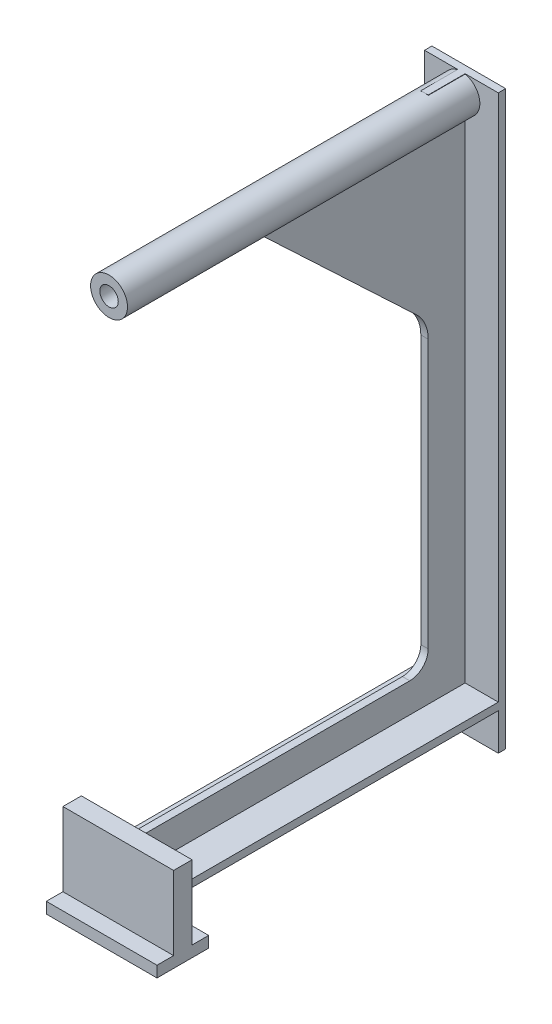
SolidWorks part; units mm, degrees
ref_plane "Front Plane" through (0, 0, 0) normal (0, 0, 1) x (1, 0, 0)
ref_plane "Top Plane" through (0, 0, 0) normal (0, 1, 0) x (1, 0, 0)
ref_plane "Right Plane" through (0, 0, 0) normal (1, 0, 0) x (0, 0, -1)
sketch "Sketch1" plane through (0, 0, 0) normal (1, 0, 0) x (0, 0, -1)
  line L0 (0, -17.2999) -> (0, 38.275) construction
  line L1 (-7, 1.5) -> (7, 1.5)
  line L2 (-7, 1.5) -> (-7, -1.5)
  line L3 (-7, -1.5) -> (7, -1.5)
  line L4 (7, 1.5) -> (7, -1.5)
  line L5 (-7, 1.5) -> (7, -1.5) construction
  line L6 (-7, -1.5) -> (7, 1.5) construction
  line L8 (-2.5, 21.5) -> (2.5, 21.5)
  line L9 (-2.5, 21.5) -> (-2.5, 1.5)
  line L10 (-2.5, 1.5) -> (2.5, 1.5)
  line L11 (2.5, 21.5) -> (2.5, 1.5)
  line L12 (-2.5, 21.5) -> (2.5, 1.5) construction
  line L13 (-2.5, 1.5) -> (2.5, 21.5) construction
  point P0 (0, 0)
  point P1 (0, 0)
  point P9 (0, 11.5)
  dimension "D1" = 5
  dimension "D2" = 20
  dimension "D3" = 14
  dimension "D4" = 3
extrude "Boss-Extrude1" add sketch "Sketch1" along normal blind 30 contours L11 L8 L9 L1 | L4 L1 L2 L3 region at (0, 0, 0) region at (0, 11.5, 0)
sketch "Sketch2" plane through (0, 0, 0) normal (0, 0, 1) x (1, 0, 0)
  line L0 (15, 1.5) -> (15, 32.2821) construction
  line L1 (30, 1.5) -> (0, 1.5) construction
  line L2 (0, 0) -> (39.1823, 0) construction
  circle A0 centre (15, 150) radius 5
  circle A1 centre (15, 150) radius 2.5
  point P4 (15, 150)
  dimension "D1" = 150
  dimension "D2" = 5
  dimension "D3" = 10
sketch "Sketch4" plane through (0, 0, 0) normal (0, 1, 0) x (1, 0, 0)
  line L0 (15, 0) -> (15, 14.6802) construction
  line L1 (30, 2.5) -> (0, 2.5) construction
  line L2 (14, 92.5) -> (16, 92.5)
  line L3 (14, 92.5) -> (14, 2.5)
  line L4 (14, 2.5) -> (16, 2.5)
  line L5 (16, 92.5) -> (16, 2.5)
  line L6 (14, 92.5) -> (16, 2.5) construction
  line L7 (14, 2.5) -> (16, 92.5) construction
  line L8 (15, 14.6802) -> (15, 36.8844) construction
  line L9 (14, 80.5) -> (16, 80.5)
  line L10 (5, 90.5) -> (25, 90.5)
  line L11 (5, 90.5) -> (5, 92.5)
  line L12 (5, 92.5) -> (25, 92.5)
  line L13 (25, 90.5) -> (25, 92.5)
  line L14 (5, 90.5) -> (25, 92.5) construction
  line L15 (5, 92.5) -> (25, 90.5) construction
  point P3 (15, 47.5)
  point P10 (15, 91.5)
  point P12 (15, 91.5)
  point P17 (15, 2.5)
  dimension "D1" = 2
  dimension "D2" = 90
  dimension "D3" = 89
  dimension "D4" = 2
  dimension "D5" = 20
  dimension "D6" = 78
extrude "Boss-Extrude2" add sketch "Sketch4" along normal blind 155 separate body contours L10 L13 L12 L5 | L3 L10 L5 L2 | L12 L11 L10 L3 | L10 L3 L9 L5 region at (15, 0, -91.5) region at (9.5, 0, -91.5) region at (20.5, 0, -91.5) region at (15, 0, -85.5)
extrude "Boss-Extrude3" add sketch "Sketch4<4>" along normal blind 20 contours L9 L3 L4 L5 region at (15, 0, -41.5)
sketch "Sketch4<4>" plane through (0, 0, 0) normal (0, 1, 0) x (1, 0, 0) same geometry as "Sketch4"
extrude "Cut-Extrude1" cut sketch "Sketch4<5>" along normal blind 10 contours L10 L3 L9 L5 | L9 L3 L4 L5 region at (15, 0, -85.5) region at (15, 0, -41.5)
sketch "Sketch4<5>" plane through (0, 0, 0) normal (0, 1, 0) x (1, 0, 0) same geometry as "Sketch4"
extrude "Boss-Extrude4" add sketch "Sketch2" against normal up to surface (92.5 mm away) and the other way blind 5 contours A0 A1 region at (10.1414, 150, 0) up to face at (15, 77.5, -92.5)
fillet "Fillet1" radius 5 2 edges at (15, 10, -90.5) (15, 20, -80.5)
ref_plane "Plane1" through (0, 11, 0) normal (0, -1, 0) x (-1, 0, 0)
sketch "Sketch5" plane through (0, 11, 0) normal (0, -1, 0) x (-1, 0, 0)
  line L10 (0, 0) -> (-32.3426, 0) construction
  line L12 (-15, 0) -> (-15, 128.8449) construction
  line L13 (-5, 92.5) -> (-25, 92.5) construction
  line L15 (-25, -0.5) -> (-5, -0.5)
  line L16 (-25, -0.5) -> (-25, 90.5)
  line L17 (-25, 90.5) -> (-5, 90.5)
  line L18 (-5, -0.5) -> (-5, 90.5)
  line L19 (-25, -0.5) -> (-5, 90.5) construction
  line L20 (-25, 90.5) -> (-5, -0.5) construction
  point P2 (-15, 0)
  point P5 (-15, 92.5)
  point P6 (-15, 45)
  point P9 (-15, 45)
  dimension "D1" = 15
  dimension "D2" = 45
ref_plane "Plane2" through (16, 0, 0) normal (1, 0, 0) x (0, 0, -1)
sketch "Sketch6" plane through (16, 0, 0) normal (1, 0, 0) x (0, 0, -1)
  line L0 (80.5, 102) -> (27.2448, 152.2552)
  line L1 (80.5, 145.101) -> (80.5, 25) construction
  line L2 (27.2448, 152.2552) -> (80.5, 152.2552)
  line L3 (80.5, 152.2552) -> (80.5, 102)
  dimension "D1" = 102
extrude "Boss-Extrude6" add sketch "Sketch6" against normal blind 2
fillet "Fillet2" radius 10 1 edges at (15, 102, -80.5)
extrude "Boss-Extrude7" add sketch "Sketch5" against normal blind 1 and the other way blind 1
